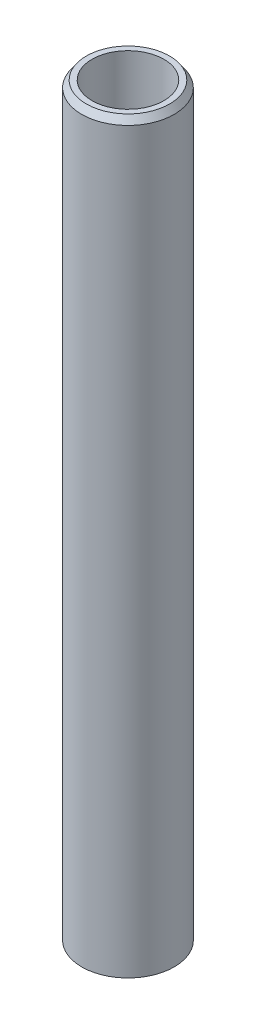
SolidWorks part; units mm, degrees
ref_plane "Front Plane" through (0, 0, 0) normal (0, 0, 1) x (1, 0, 0)
ref_plane "Top Plane" through (0, 0, 0) normal (0, 1, 0) x (1, 0, 0)
ref_plane "Right Plane" through (0, 0, 0) normal (1, 0, 0) x (0, 0, -1)
sketch "Sketch1" plane through (0, 0, 0) normal (0, 1, 0) x (1, 0, 0)
  circle A0 centre (0, 0) radius 22.5
  dimension "SHAFT_OD" = 45
extrude "Boss-Extrude1" add sketch "Sketch1" along normal blind 364.7097
sketch "Sketch2" plane through (0, 0, 0) normal (0, 1, 0) x (1, 0, 0)
  circle A0 centre (0, 0) radius 17.4785
  dimension "BORE_D" = 34.9569
extrude "Cut-Extrude1" cut sketch "Sketch2" along normal through all
chamfer "Chamfer1" distance 3.2541 angle 34.709 2 edges at (0, 364.7097, 22.5) (0, 0, 22.5) first distance on face at (0, 364.7097, 22.5) first distance on face at (0, 0, 17.4785)
